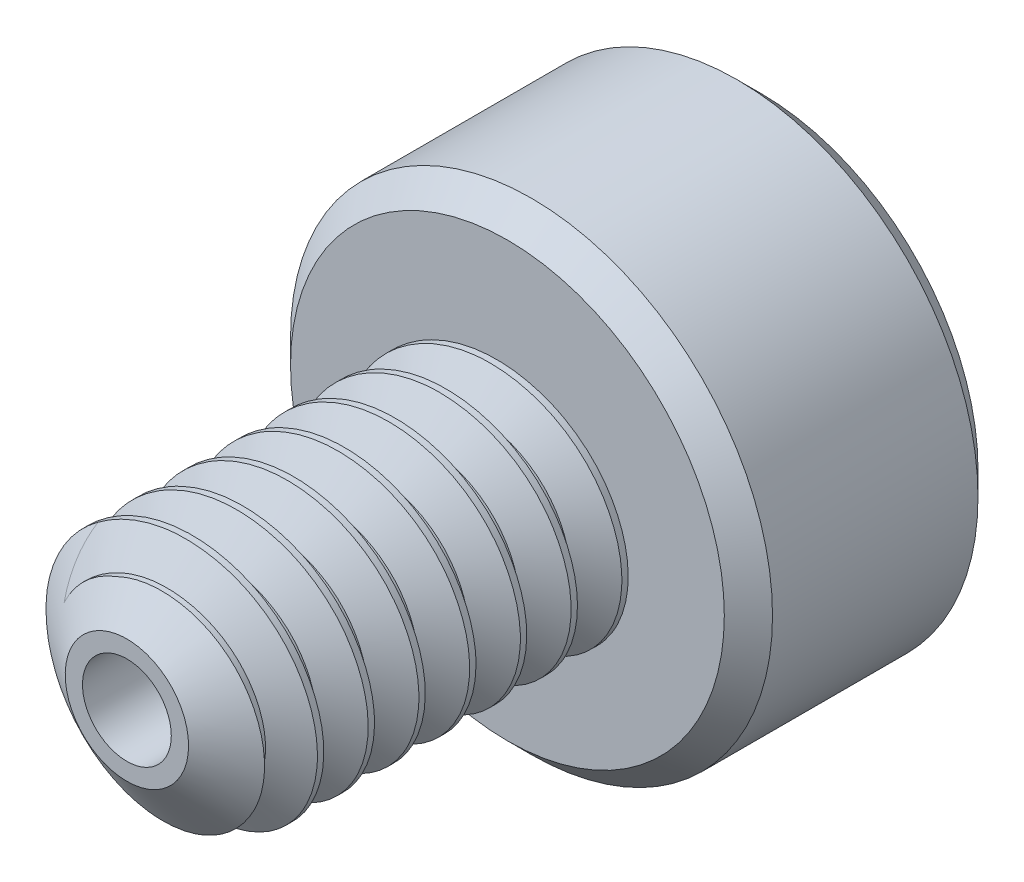
SolidWorks part; units mm, degrees
other "DetailItem1"
ref_plane "Front Plane" through (0, 0, 0) normal (0, 0, 1) x (1, 0, 0)
ref_plane "Top Plane" through (0, 0, 0) normal (0, 1, 0) x (1, 0, 0)
ref_plane "Right Plane" through (0, 0, 0) normal (1, 0, 0) x (0, 0, -1)
sketch "Sketch1" plane through (0, 0, 0) normal (0, 0, 1) x (1, 0, 0)
  circle A0 centre (0, 0) radius 1
  dimension "OD" = 2
extrude "Extrude1" add sketch "Sketch1" against normal blind 3
sketch "Sketch2" plane through (0, 0, 0) normal (0, 0, 1) x (1, 0, 0)
  circle A0 centre (0, 0) radius 1 construction
  circle A1 centre (0, 0) radius 1
curve "Helix/Spiral1" pitch 0.4 height 3.4 radius 1 centre (0, 0, 0) axis (0, 0, -1) start towards (0, 1, 0) parameters "pitch"=0.4
sketch "Sketch3" plane through (0, 0, 0) normal (1, 0, 0) x (0, 0, -1)
  line L0 (-0.35, 1) -> (-0.2, 0.7402)
  line L1 (-0.2, 0.7402) -> (-0.15, 0.7402)
  line L2 (-0.15, 0.7402) -> (0, 1)
  line L3 (-0.35, 1) -> (0, 1)
  line L4 (-0.175, 1) -> (-0.175, 0.7402) construction
  line L5 (-0.275, 0.8701) -> (-0.075, 0.8701) construction
  line L6 (0, 1) -> (0, -1) construction
  dimension "D1" = 0.05
  dimension "D2" = 0.2
  dimension "D3" = 60
sweep "Cut-Sweep1" cut profiles "Sketch3" path "Helix/Spiral1" align with end faces yes
sketch "Sketch4" plane through (0, 0, 0) normal (1, 0, 0) x (0, 0, -1)
  line L0 (0.3598, 1) -> (0, 0.4862)
  line L1 (0, 0.4862) -> (0, 1)
  line L2 (0.3598, 1) -> (0, 1)
  line L3 (-0.35, 1) -> (0, 1) construction
  line L4 (0, 0) -> (7.0209, 0) construction
  dimension "D1" = 55
  dimension "D2" = 0.254
revolve "Cut-Revolve1" cut sketch "Sketch4" angle 360 about L4
sketch "Sketch6" plane through (0, 0, -3) normal (0, 0, -1) x (-1, 0, 0)
  circle A0 centre (0, 0) radius 1.9
  dimension "head dia" = 3.8
extrude "Extrude2" add sketch "Sketch6" along normal blind 2
sketch "Sketch7" plane through (0, 0, -5) normal (0, 0, -1) x (-1, 0, 0)
  line L1 (0, 0.866) -> (-0.75, 0.433)
  line L2 (-0.75, 0.433) -> (-0.75, -0.433)
  line L3 (-0.75, -0.433) -> (0, -0.866)
  line L4 (0, -0.866) -> (0.75, -0.433)
  line L5 (0.75, -0.433) -> (0.75, 0.433)
  line L6 (0.75, 0.433) -> (0, 0.866)
  circle A0 centre (0, 0) radius 0.75 construction
  dimension "hex dia" = 1.5
extrude "Cut-Extrude1" cut sketch "Sketch7" against normal blind 1.125
sketch "Sketch8" plane through (0, 0, -5) normal (0, 0, -1) x (-1, 0, 0)
  circle A0 centre (0, 0) radius 0.866
extrude "Cut-Extrude2" cut sketch "Sketch8" against normal through all draft 45
chamfer "Chamfer1" distance 0.19 angle 45 2 edges at (-1.9, 0, -5) (-1.9, 0, -3)
sketch "Sketch10" plane through (0, 0, -3) normal (0, 0, 1) x (1, 0, 0)
  circle A1 centre (0, 0) radius 1
  circle A2 centre (0, 0) radius 1
  dimension "D1" = 0
ref_plane "Plane1" through (0, 0, 0) normal (0, 0, 1) x (1, 0, 0)
extrude "partial thread" [suppressed] add sketch "Sketch10" along normal up to surface (12.7 mm away) separate body
chamfer "Chamfer2" [suppressed] distance 0.04 angle 45
combine bodies "Combine1" [suppressed] operation type add bodies to combine 107 108
sketch "Sketch9" plane through (0, 0, 0) normal (1, 0, 0) x (0, 0, -1)
  line L0 (0, 1) -> (0, -1) construction
  line L1 (1, 1) -> (1, -1) construction
  dimension "D1" = 1
sketch "Sketch11" plane through (0, 0, 0) normal (0, 0, 1) x (1, 0, 0)
  circle A0 centre (0, 0) radius 0.35
  dimension "Vent Dia" = 0.7
extrude "Cut-Extrude3" cut sketch "Sketch11" against normal through all
equation "\"D3@Helix/Spiral1\" = \"screw length@Extrude1\"+\"pitch@Helix/Spiral1\""
equation "\"D1@Sketch3\" = \"pitch@Helix/Spiral1\"*.125"
equation "\"D2@Sketch3\" = \"pitch@Helix/Spiral1\"*.5"
equation "\"D1@Cut-Extrude1\" = \"hex dia@Sketch7\"*.75"
equation "\"D1@Chamfer1\" = \"head dia@Sketch6\"*.05"
equation "\"D1@Sketch9\" = \"pitch@Helix/Spiral1\"*2.5"
equation "\"D1@Chamfer2\"=\"OD@Sketch1\"*.02"
